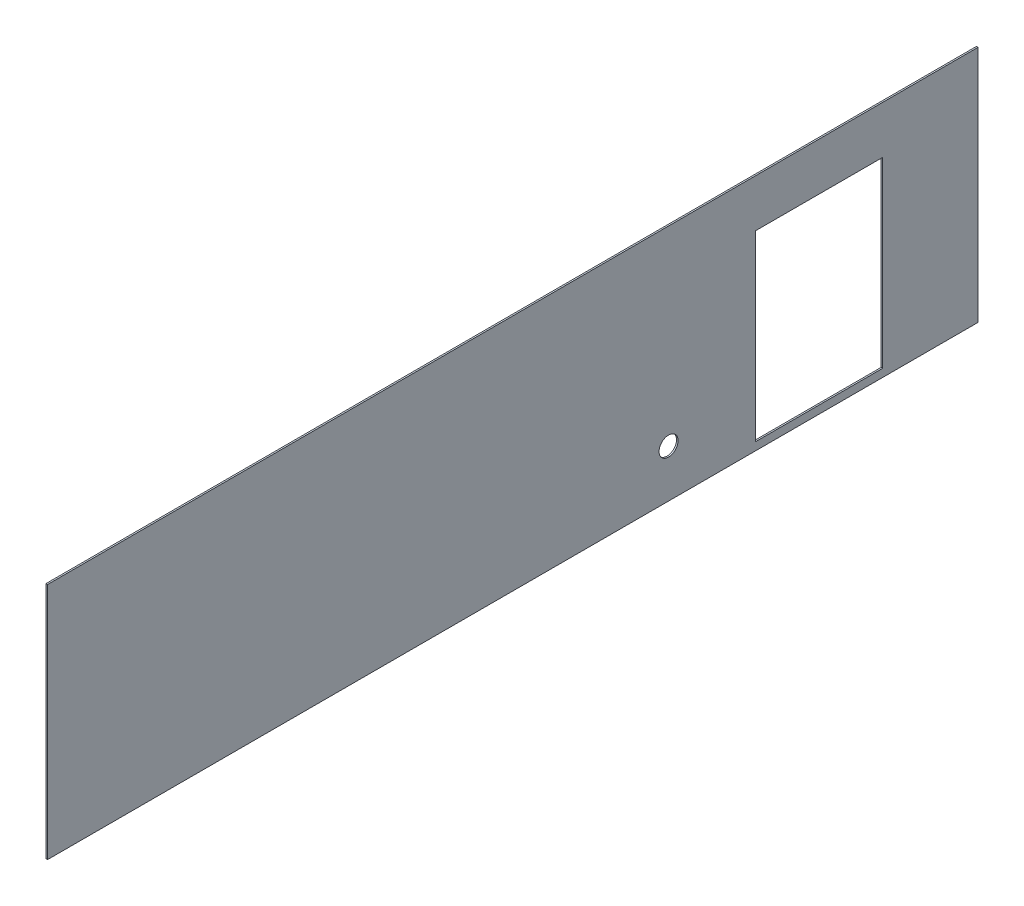
SolidWorks part; units mm, degrees
ref_plane "Front Plane" through (0, 0, 0) normal (0, 0, 1) x (1, 0, 0)
ref_plane "Top Plane" through (0, 0, 0) normal (0, 1, 0) x (1, 0, 0)
ref_plane "Right Plane" through (0, 0, 0) normal (1, 0, 0) x (0, 0, -1)
sketch "Sketch1" plane through (0, 0, 0) normal (0, 0, 1) x (1, 0, 0)
  line L1 (-236.5375, -47.625) -> (236.5375, -47.625)
  line L2 (-236.5375, -47.625) -> (-236.5375, 47.625)
  line L3 (-236.5375, 47.625) -> (236.5375, 47.625)
  line L4 (236.5375, -47.625) -> (236.5375, 47.625)
  line L5 (-236.5375, -47.625) -> (236.5375, 47.625) construction
  line L6 (-236.5375, 47.625) -> (236.5375, -47.625) construction
  point P0 (0, 0)
  dimension "D1" = 473.075
  dimension "D2" = 95.25
extrude "Boss-Extrude1" add sketch "Sketch1" along normal blind 3.175
sketch "Sketch3" plane through (0, 0, 3.175) normal (0, 0, 1) x (1, 0, 0)
  line L0 (0, -47.625) -> (0, -19.05)
  line L1 (-236.5375, -47.625) -> (236.5375, -47.625) construction
  line L3 (-39.37, -18.923) -> (39.37, -18.923)
  line L4 (-39.37, -18.923) -> (-39.37, 32.385)
  line L5 (-39.37, 32.385) -> (39.37, 32.385)
  line L6 (39.37, -18.923) -> (39.37, 32.385)
  dimension "D1" = 28.575
  dimension "D2" = 78.74
  dimension "D3" = 39.37
  dimension "D4" = 51.308
  dimension "D5" = 28.702
extrude "Cut-Extrude2" cut sketch "Sketch3" against normal through all contours L3 L6 L5 L4 region at (0, 6.731, 3.175)
sketch "Sketch4" plane through (0, 0, 3.175) normal (0, 0, 1) x (1, 0, 0)
  line L0 (-236.5375, -47.625) -> (236.5375, -47.625) construction
  line L1 (39.37, -18.923) -> (39.37, 32.385) construction
  circle A0 centre (37.592, -35.814) radius 8.255
  dimension "D1" = 16.51
  dimension "D2" = 11.811
  dimension "D3" = 1.778
extrude "Cut-Extrude3" cut sketch "Sketch4" against normal through all
sketch "Sketch5" plane through (0, 0, 3.175) normal (0, 0, 1) x (1, 0, 0)
  line L0 (39.37, -18.923) -> (39.37, 32.385) construction
  line L1 (-39.37, 32.385) -> (39.37, 32.385) construction
  line L2 (0, 0) -> (0, 11.1381)
  line L3 (0, 0) -> (6.9433, 0)
  circle A0 centre (44.196, 40.259) radius 1.5875
  circle A1 centre (44.196, -24.765) radius 1.5875
  circle A2 centre (-44.196, -24.765) radius 1.5875
  circle A3 centre (-44.196, 40.259) radius 1.5875
  dimension "D1" = 3.175
  dimension "D3" = 7.874
  dimension "D4" = 65.024
  dimension "D5" = 0
  dimension "D2" = 4.826
extrude "Cut-Extrude4" cut sketch "Sketch5" against normal through all contours A3 | A0 | A2 | A1 region at (44.196, 40.259, 3.175) region at (44.196, -24.765, 3.175) region at (-44.196, -24.765, 3.175) region at (-44.196, 40.259, 3.175)
sketch "Sketch6" plane through (0, 0, 0) normal (0, 0, -1) x (-1, 0, 0)
  line L0 (236.5375, -47.625) -> (-236.5375, -47.625) construction
  line L1 (236.5375, 47.625) -> (233.3625, 47.625)
  line L2 (236.5375, 47.625) -> (236.5375, -47.625)
  line L3 (236.5375, -47.625) -> (233.3625, -47.625)
  line L4 (233.3625, 47.625) -> (233.3625, -47.625)
  dimension "D1" = 3.175
extrude "Boss-Extrude2" add sketch "Sketch6" along normal blind 371.948
sketch "Sketch7" plane through (-236.5375, 0, 0) normal (-1, 0, 0) x (0, 0, 1)
  line L0 (3.175, 47.625) -> (-371.948, 47.625) construction
  line L1 (-333.848, 28.575) -> (-283.048, 28.575)
  line L2 (-333.848, 28.575) -> (-333.848, -44.45)
  line L3 (-333.848, -44.45) -> (-283.048, -44.45)
  line L4 (-283.048, 28.575) -> (-283.048, -44.45)
  line L5 (-371.948, -47.625) -> (-371.948, 47.625) construction
  line L6 (3.175, -47.625) -> (-371.948, -47.625) construction
  circle A0 centre (-248.25, -28.575) radius 3.81
  dimension "D5" = 123.698
  dimension "D6" = 19.05
  dimension "D1" = 19.05
  dimension "D2" = 50.8
  dimension "D3" = 38.1
  dimension "D4" = 3.175
extrude "Cut-Extrude5" cut sketch "Sketch7" against normal blind 381
sketch "Sketch8" plane through (0, 0, 3.175) normal (0, 0, 1) x (1, 0, 0)
  line L0 (88.9, 27.94) -> (215.9, 27.94) construction
  line L1 (88.9, 31.75) -> (215.9, 31.75)
  line L2 (88.9, 24.13) -> (215.9, 24.13)
  line L3 (88.9, 8.7536) -> (215.9, 8.7536) construction
  line L4 (88.9, 12.5636) -> (215.9, 12.5636)
  line L5 (88.9, 4.9436) -> (215.9, 4.9436)
  line L6 (88.9, -10.0663) -> (215.9, -10.0663) construction
  line L7 (88.9, -6.2563) -> (215.9, -6.2563)
  line L8 (88.9, -13.8763) -> (215.9, -13.8763)
  line L9 (88.9, -28.656) -> (215.9, -28.656) construction
  line L10 (88.9, -24.846) -> (215.9, -24.846)
  line L11 (88.9, -32.466) -> (215.9, -32.466)
  line L15 (-88.9, -28.656) -> (-215.9, -28.656) construction
  line L18 (-88.9, -24.846) -> (-215.9, -24.846)
  line L21 (-88.9, -32.466) -> (-215.9, -32.466)
  line L24 (-88.9, -10.0663) -> (-215.9, -10.0663) construction
  line L27 (-88.9, -6.2563) -> (-215.9, -6.2563)
  line L28 (-88.9, -13.8763) -> (-215.9, -13.8763)
  line L29 (-88.9, 8.7536) -> (-215.9, 8.7536) construction
  line L30 (-88.9, 12.5636) -> (-215.9, 12.5636)
  line L31 (-88.9, 4.9436) -> (-215.9, 4.9436)
  line L32 (-88.9, 27.94) -> (-215.9, 27.94) construction
  line L33 (-88.9, 31.75) -> (-215.9, 31.75)
  line L34 (-88.9, 24.13) -> (-215.9, 24.13)
  arc A0 (88.9, 31.75) -> (88.9, 24.13) centre (88.9, 27.94) ccw
  arc A1 (215.9, 24.13) -> (215.9, 31.75) centre (215.9, 27.94) ccw
  arc A2 (88.9, 12.5636) -> (88.9, 4.9436) centre (88.9, 8.7536) ccw
  arc A3 (215.9, 4.9436) -> (215.9, 12.5636) centre (215.9, 8.7536) ccw
  arc A4 (88.9, -6.2563) -> (88.9, -13.8763) centre (88.9, -10.0663) ccw
  arc A5 (215.9, -13.8763) -> (215.9, -6.2563) centre (215.9, -10.0663) ccw
  arc A6 (88.9, -24.846) -> (88.9, -32.466) centre (88.9, -28.656) ccw
  arc A7 (215.9, -32.466) -> (215.9, -24.846) centre (215.9, -28.656) ccw
  arc A16 (-88.9, -24.846) -> (-88.9, -32.466) centre (-88.9, -28.656) cw
  arc A17 (-215.9, -32.466) -> (-215.9, -24.846) centre (-215.9, -28.656) cw
  arc A18 (-88.9, -6.2563) -> (-88.9, -13.8763) centre (-88.9, -10.0663) cw
  arc A19 (-215.9, -13.8763) -> (-215.9, -6.2563) centre (-215.9, -10.0663) cw
  arc A20 (-88.9, 12.5636) -> (-88.9, 4.9436) centre (-88.9, 8.7536) cw
  arc A21 (-215.9, 4.9436) -> (-215.9, 12.5636) centre (-215.9, 8.7536) cw
  arc A22 (-88.9, 31.75) -> (-88.9, 24.13) centre (-88.9, 27.94) cw
  arc A23 (-215.9, 24.13) -> (-215.9, 31.75) centre (-215.9, 27.94) cw
  point P2 (152.4, 27.94)
  point P7 (152.4, 8.7536)
  point P16 (152.4, -10.0663)
  point P21 (152.4, -28.656)
  point P32 (-152.4, -28.656)
  point P39 (-152.4, -10.0663)
  point P46 (-152.4, 8.7536)
  point P53 (-152.4, 27.94)
extrude "Cut-Extrude6" cut sketch "Sketch8" against normal blind 381 contours L11 A7 L10 A6 | L8 A5 L7 A4 | L5 A3 L4 A2 | L2 A1 L1 A0 | L2 A1 L1 A0 | L33 A23 L34 A22 | L30 A21 L31 A20 | L27 A19 L28 A18 | L18 A17 L21 A16 region at (152.4, 27.94, 3.175) region at (152.4, 8.7536, 3.175) region at (152.4, -10.0663, 3.175) region at (152.4, -28.656, 3.175)
sketch "Sketch12" plane through (-233.3625, 0, 0) normal (1, 0, 0) x (0, 0, -1)
  line L1 (0, 47.625) -> (371.948, 47.625)
  line L2 (0, 47.625) -> (0, -47.625)
  line L3 (0, -47.625) -> (371.948, -47.625)
  line L4 (371.948, 47.625) -> (371.948, -47.625)
extrude "Cut-Extrude7" cut sketch "Sketch12" against normal blind 2.54
sketch "Sketch14" plane through (0, 0, 3.175) normal (0, 0, 1) x (1, 0, 0)
  line L1 (236.5375, 47.625) -> (-236.5375, 47.625)
  line L2 (236.5375, 47.625) -> (236.5375, -47.625)
  line L3 (236.5375, -47.625) -> (-236.5375, -47.625)
  line L4 (-236.5375, 47.625) -> (-236.5375, -47.625)
extrude "Cut-Extrude8" cut sketch "Sketch14" against normal up to surface (3.175 mm away) up to face at (152.4, -10.0663, 0)
